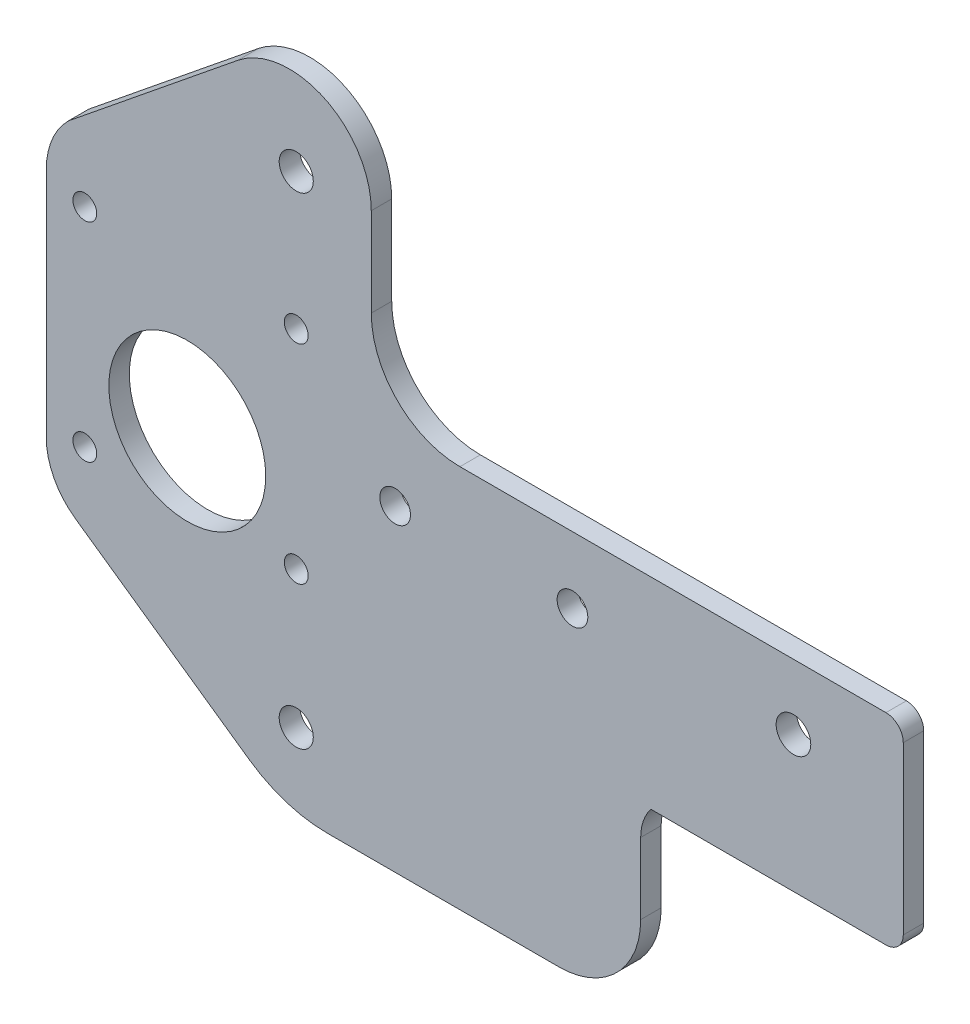
SolidWorks part; units mm, degrees
ref_plane "Front Plane" through (0, 0, 0) normal (0, 0, 1) x (1, 0, 0)
ref_plane "Top Plane" through (0, 0, 0) normal (0, 1, 0) x (1, 0, 0)
ref_plane "Right Plane" through (0, 0, 0) normal (1, 0, 0) x (0, 0, -1)
sketch "Sketch1" plane through (0, 0, 0) normal (0, 0, 1) x (1, 0, 0)
  line L0 (0, 0) -> (0, -29.5)
  line L1 (0, -29.5) -> (-37, -29.5)
  line L2 (0, 0) -> (-65, 0)
  line L3 (-78, 13) -> (-78, 26)
  line L4 (-97.5518, 35.3258) -> (-122.4205, 15.1875)
  line L5 (-125.65, 7.4017) -> (-125.65, -26.5983)
  line L6 (-89, 5.5) -> (-89, -25) construction
  line L7 (-120, 5.5) -> (-89, 5.5) construction
  line L8 (-121.3858, -34.7898) -> (-95.8858, -52.6451)
  line L9 (-84.4142, -56.2621) -> (-50.5, -56.2621)
  line L10 (-38.5, -44.2621) -> (-38.5, -33.8301)
  line L11 (-104.5, -9.75) -> (-104.5, 5.5) construction
  line L12 (-104.5, -9.75) -> (-89, -9.75) construction
  arc A0 (-78, 13) -> (-65, 0) centre (-65, 13) ccw
  arc A1 (-78, 26) -> (-97.5518, 35.3258) centre (-90, 26) ccw
  arc A2 (-122.4205, 15.1875) -> (-125.65, 7.4017) centre (-114.65, 7.4017) ccw
  arc A3 (-125.65, -26.5983) -> (-121.3858, -34.7898) centre (-115.65, -26.5983) ccw
  arc A4 (-95.8858, -52.6451) -> (-84.4142, -56.2621) centre (-84.4142, -36.2621) ccw
  arc A5 (-50.5, -56.2621) -> (-38.5, -44.2621) centre (-50.5, -44.2621) ccw
  arc A6 (-37, -29.5) -> (-38.5, -33.8301) centre (-31.5, -33.8301) ccw
  circle A7 centre (-16.102, -9.552) radius 2.54
  circle A8 centre (-48.5, -9.75) radius 2.25
  circle A9 centre (-74.5, -9.75) radius 2.25
  circle A10 centre (-89, 5.5) radius 1.75
  circle A11 centre (-89, 25.5) radius 2.5
  circle A12 centre (-89, -25) radius 1.75
  circle A13 centre (-89, -45.112) radius 2.5
  circle A14 centre (-104.975, -15.4503) radius 11.5
  circle A15 centre (-120, 5.5) radius 1.75
  circle A16 centre (-120, -25) radius 1.75
  dimension "D4" = 24
  dimension "D5" = 26
  dimension "D12" = 20
  dimension "D16" = 14
  dimension "D17" = 24
  dimension "D19" = 5.08
  dimension "D20" = 4.5
  dimension "D21" = 4.5
  dimension "D22" = 31
  dimension "D23" = 5
  dimension "D25" = 5
  dimension "D11" = 3.5
  dimension "D1" = 65
  dimension "D2" = 29.5
  dimension "D3" = 37
  dimension "D6" = 13
  dimension "D7" = 32
  dimension "D8" = 51
  dimension "D10" = 34
  dimension "D14" = 125
  dimension "D15" = 25.5
  dimension "D18" = 1.5
  dimension "D29" = 72.898
  dimension "D30" = 9.75
  dimension "D31" = 9.75
  dimension "D34" = 25.5
  dimension "D37" = 70.612
  dimension "D39" = 35.56
  dimension "D40" = 48.5
  dimension "D41" = 74.5
  dimension "D42" = 89
extrude "Boss-Extrude1" add sketch "Sketch1" along normal blind 3
fillet "Fillet2" radius 2.54 2 edges at (0, 0, 1.5) (0, -29.5, 1.5)
